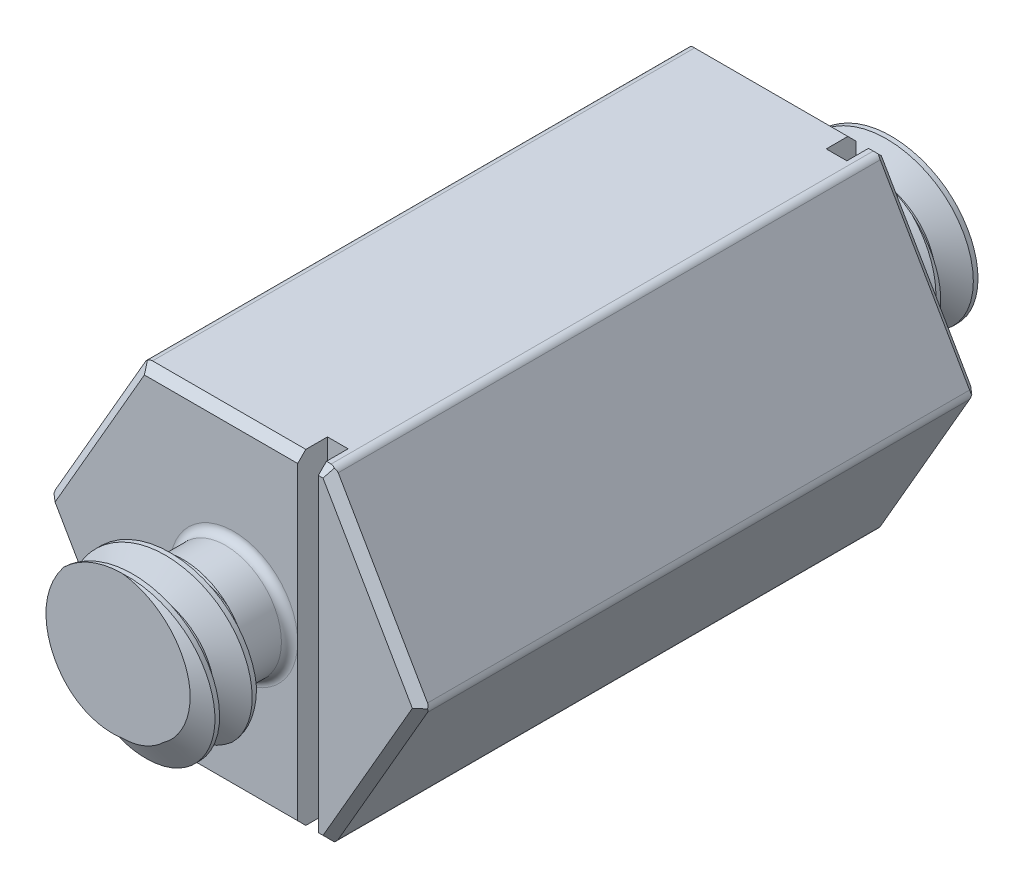
SolidWorks part; units mm, degrees
material "6061-T6 (SS)"
ref_plane "Front Plane" through (0, 0, 0) normal (0, 0, 1) x (1, 0, 0)
ref_plane "Top Plane" through (0, 0, 0) normal (0, 1, 0) x (1, 0, 0)
ref_plane "Right Plane" through (0, 0, 0) normal (1, 0, 0) x (0, 0, -1)
sketch "Sketch1" plane through (0, 0, 0) normal (0, 0, 1) x (1, 0, 0)
  line L0 (0, 0) -> (3.2079, 0) construction
  line L1 (1.604, 2.7781) -> (-1.604, 2.7781)
  line L2 (-1.604, 2.7781) -> (-3.2079, 0)
  line L3 (-3.2079, 0) -> (-1.604, -2.7781)
  line L4 (-1.604, -2.7781) -> (1.604, -2.7781)
  line L5 (1.604, -2.7781) -> (3.2079, 0)
  line L6 (3.2079, 0) -> (1.604, 2.7781)
  circle A0 centre (0, 0) radius 2.7781 construction
sketch "Sketch2" plane through (0, 0, 0) normal (1, 0, 0) x (0, 0, -1)
  line L0 (-4.7625, 2.7781) -> (4.7625, 2.7781) construction
  line L1 (-11.1125, 0) -> (-4.7625, 0) construction
  line L2 (-11.1125, 1.4224) -> (-11.1125, -1.4224) construction
  line L3 (-11.7078, 1.4911) -> (-11.0728, 1.4911) construction
  line L4 (-11.0728, 1.4911) -> (-11.3903, 0.9412) construction
  line L5 (-11.3903, 0.9412) -> (-11.7078, 1.4911) construction
  line L6 (-11.6681, 1.4224) -> (-11.1125, 1.4224) construction
  line L7 (-11.43, 1.01) -> (-11.3506, 1.01) construction
  line L8 (-11.3903, 1.01) -> (-11.3903, 0.9412) construction
  line L9 (-11.3903, 1.4224) -> (-11.3903, 1.4911) construction
  line L10 (4.7625, 0) -> (11.1125, 0) construction
  line L11 (-4.7625, 0.9525) -> (-5.5245, 0.9525) construction
  point P2 (0, 2.7781)
  point P20 (9.525, -1.4224)
sketch "Sketch3" plane through (0, 0, 0) normal (1, 0, 0) x (0, 0, -1)
  line L0 (11.1125, 0) -> (-11.1125, 0)
  line L1 (-11.1125, 0) -> (-11.1125, 1.2128)
  line L2 (-11.1125, 1.4224) -> (-11.1125, -1.4224) construction
  line L3 (-11.1125, 1.2128) -> (-10.903, 1.4224)
  line L4 (-10.903, 1.4224) -> (-5.7958, 1.4224)
  line L5 (-4.7625, 0.9525) -> (-4.7625, 2.7781)
  line L6 (-4.7625, 2.7781) -> (4.7625, 2.7781)
  line L7 (4.7625, 2.7781) -> (4.7625, 0.9525)
  line L8 (5.7958, 1.4224) -> (10.9029, 1.4224)
  line L9 (10.9029, 1.4224) -> (11.1125, 1.2129)
  line L10 (11.1125, 1.2129) -> (11.1125, 0)
  line L11 (-5.7958, 1.4224) -> (-5.5245, 0.9525)
  line L12 (-5.5245, 0.9525) -> (-4.7625, 0.9525)
  line L13 (5.7958, 1.4224) -> (5.5245, 0.9525)
  line L14 (5.5245, 0.9525) -> (4.7625, 0.9525)
  dimension "D1" = 0.2095
  dimension "D2" = 45
  dimension "D3" = 60
revolve "Revolve1" add sketch "Sketch3" angle 360 about L1
sketch "Sketch4" plane through (0, 0, 0) normal (0, 0, 1) x (1, 0, 0)
  line L1 (-3.2079, 0) -> (-1.604, -2.7781)
  line L2 (-1.604, -2.7781) -> (1.604, -2.7781)
  line L3 (1.604, -2.7781) -> (3.2079, 0)
  line L4 (3.2079, 0) -> (1.604, 2.7781)
  line L5 (1.604, 2.7781) -> (-1.604, 2.7781)
  line L6 (-1.604, 2.7781) -> (-3.2079, 0)
  line L7 (1.604, 2.7781) -> (-1.604, 2.7781) construction
  circle A0 centre (0, 0) radius 2.7781 construction
  circle A1 centre (0, 0) radius 2.7781 construction
extrude "Boss-Extrude1" add sketch "Sketch4" against normal up to vertex (4.7625 mm away) and the other way up to vertex (4.7625 mm away) up to point (0, 2.7781, -4.7625) other way up to point (0, 2.7781, 4.7625)
chamfer "Chamfer1" distance 0.1389 angle 45 12 edges at (-2.4059, 1.3891, -4.7625) (-2.4059, -1.3891, -4.7625) (0, -2.7781, -4.7625) (2.4059, -1.3891, -4.7625) (2.4059, 1.3891, -4.7625) (0, 2.7781, -4.7625) (0, -2.7781, 4.7625) (-2.4059, -1.3891, 4.7625) (-2.4059, 1.3891, 4.7625) (0, 2.7781, 4.7625) (2.4059, 1.3891, 4.7625) (2.4059, -1.3891, 4.7625)
fillet "Fillet1" radius 0.1389 8 edges at (-3.2079, 0, 0) (-1.604, -2.7781, 0) (1.604, -2.7781, 0) (3.2079, 0, 0) (-1.604, 2.7781, 0) (1.604, 2.7781, 0) (0.9525, 0, -4.7625) (0.9525, 0, 4.7625)
sketch "Sketch5" plane through (0, 0, 11.1125) normal (0, 0, 1) x (1, 0, 0)
  circle A0 centre (0, 0) radius 1.4224
curve "Helix/Spiral1" pitch 0.635 height 6.0985 radius 1.4224 centre (0, 0, 11.1125) axis (0, 0, -1) start towards (0, 1, 0)
sketch "Sketch6" plane through (0, 0, 0) normal (1, 0, 0) x (0, 0, -1)
  line L0 (-11.43, 1.01) -> (-11.3506, 1.01)
  line L1 (-11.3506, 1.01) -> (-11.0927, 1.4568)
  line L2 (-11.0728, 1.4911) -> (-11.3903, 0.9412) construction
  line L3 (-11.0927, 1.4568) -> (-11.688, 1.4568)
  line L4 (-11.3903, 0.9412) -> (-11.7078, 1.4911) construction
  line L5 (-11.688, 1.4568) -> (-11.43, 1.01)
  line L6 (-11.3903, 1.4224) -> (-11.3903, 1.4911) construction
  point P12 (-11.3903, 1.4568)
sweep "Cut-Sweep1" cut profiles "Sketch6" path "Helix/Spiral1" align with end faces yes
pattern_circular "CirPattern1" count 2 over 360 about axis through (0, 0, 0) along (1, 0, 0) of "Cut-Sweep1"
sketch "Sketch7" plane through (0, 0, 11.1125) normal (0, 0, 1) x (1, 0, 0)
  circle A0 centre (0, 0) radius 2.2767
extrude "Cut-Extrude1" cut sketch "Sketch7" against normal blind 4.445
extrude "Cut-Extrude2" cut sketch "Sketch7<2>" along normal blind 4.445 from surface starting at face at (0.0224, 0.2504, -11.1125)
sketch "Sketch7<2>" plane through (0, 0, 11.1125) normal (0, 0, 1) x (1, 0, 0) same geometry as "Sketch7"
sketch "Sketch8" plane through (0, 0, -4.7625) normal (0, 0, -1) x (-1, 0, 0)
  line L0 (-1.5238, 2.6392) -> (-3.0475, 0) construction
  line L1 (-1.0914, 0) -> (-1.4436, 0)
  line L2 (-1.0914, 0) -> (-1.0914, -2.7781)
  line L3 (-1.0914, -2.7781) -> (-1.4436, -2.7781)
  line L4 (-1.4436, 0) -> (-1.4436, -2.7781)
  line L5 (-1.0914, 0) -> (-1.4436, 0)
  line L6 (-1.0914, 0) -> (-1.0914, 2.7781)
  line L7 (-1.0914, 2.7781) -> (-1.4436, 2.7781)
  line L8 (-1.4436, 0) -> (-1.4436, 2.7781)
  line L10 (-1.5238, -2.7781) -> (1.5238, -2.7781) construction
  line L11 (-1.5238, 2.7781) -> (1.5238, 2.7781) construction
  circle A0 centre (0, 0) radius 1.0914 construction
  line M12 (1.5238, 2.6392) -> (-1.5238, 2.6392)
  line M15 (-1.5238, -2.6392) -> (1.5238, -2.6392)
extrude "Cut-Extrude3" cut sketch "Sketch8" against normal blind 0.508 contours L8 L1 L6 M12 | L1 L4 L2 M15 | L4 L3 L2 M15 | L8 L6 L7 M12 region at (1.2675, -1.3196, -4.7625) region at (1.2675, 1.3196, -4.7625) region at (1.2675, -2.7087, -4.7625) region at (1.2675, 2.7087, -4.7625)
extrude "Cut-Extrude4" cut sketch "Sketch8<3>" along normal blind 0.508 from surface contours L8 L6 L7 M12 | L8 L1 L6 M12 | L1 L4 L2 M15 | L4 L3 L2 M15 region at (1.2675, -1.3196, -4.7625) region at (1.2675, 1.3196, -4.7625) region at (1.2675, -2.7087, -4.7625) region at (1.2675, 2.7087, -4.7625) starting at face at (-1.0914, 0, 4.7625)
sketch "Sketch8<3>" plane through (0, 0, -4.7625) normal (0, 0, -1) x (-1, 0, 0) same geometry as "Sketch8"
equation "\"Pitch/8@Sketch2\" = \"Thread Pitch@Sketch2\" / 8"
equation "\"D1@Sketch3\"=\"Thread Pitch@Sketch2\"*.33"
equation "\"D1@Chamfer1\"=\"Hex Size@Sketch1\" * .025"
equation "\"D1@Fillet1\"=\"Hex Size@Sketch1\" * .025"
equation "\"D3@Helix/Spiral1\" = \"Thread Length@Sketch2\" - \"Min Step Length@Sketch2\" * .33"
equation "\"D4@Helix/Spiral1\"=\"Thread Pitch@Sketch2\""
equation "\"Thread Note@Sketch2\" = \"Thread Pitch@Sketch2\" * 2.5"
